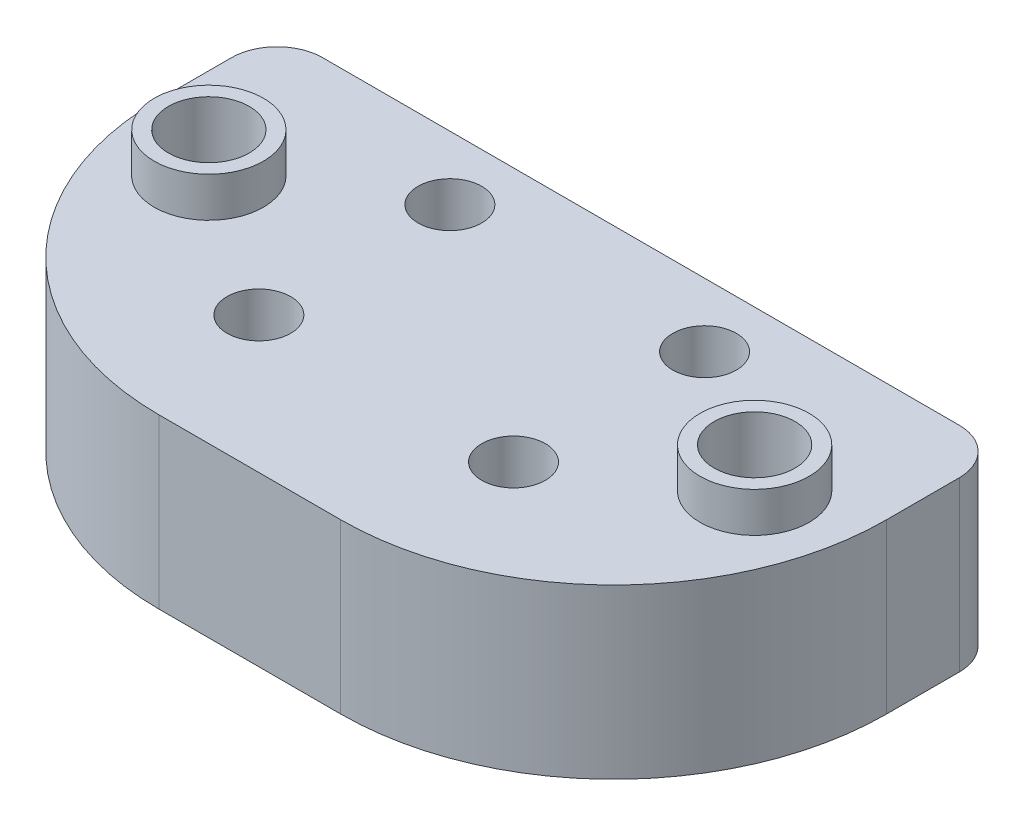
SolidWorks part; units mm, degrees
ref_plane "Front Plane" through (0, 0, 0) normal (0, 0, 1) x (1, 0, 0)
ref_plane "Top Plane" through (0, 0, 0) normal (0, 1, 0) x (1, 0, 0)
ref_plane "Right Plane" through (0, 0, 0) normal (1, 0, 0) x (0, 0, -1)
sketch "Sketch1" plane through (0, 0, 0) normal (0, 1, 0) x (1, 0, 0)
  line L0 (60, -8) -> (80, -8)
  line L1 (0, 0) -> (80, 0)
  line L2 (0, 0) -> (0, -51)
  line L3 (0, -51) -> (80, -51)
  line L4 (80, 0) -> (80, -51)
  line L5 (20, -8) -> (60, -8)
  line L6 (20, -8) -> (20, -43)
  line L7 (20, -43) -> (60, -43)
  line L8 (60, -8) -> (60, -43)
  line L9 (0, -8) -> (20, -8)
  circle A0 centre (26, -15) radius 3.5
  circle A1 centre (54, -15) radius 3.5
  circle A2 centre (54, -36) radius 3.5
  circle A3 centre (26, -36) radius 3.5
  circle A4 centre (10, -25.5) radius 4.445
  circle A5 centre (70, -25.5) radius 4.445
  circle A6 centre (26, -15) radius 4.35
  circle A7 centre (54, -15) radius 4.35
  circle A8 centre (26, -36) radius 4.35
  circle A9 centre (54, -36) radius 4.35
  circle A10 centre (70, -25.5) radius 6
  circle A11 centre (10, -25.5) radius 6
  dimension "D7" = 7
  dimension "D8" = 8.89
  dimension "D16" = 8.7
  dimension "D17" = 12
  dimension "D1" = 21
  dimension "D2" = 28
  dimension "D3" = 26
  dimension "D4" = 80
  dimension "D5" = 51
  dimension "D6" = 15
  dimension "D9" = 10
  dimension "D10" = 10
  dimension "D11" = 40
  dimension "D12" = 35
  dimension "D13" = 7
  dimension "D14" = 6
  dimension "D15" = 25.5
extrude "Boss-Extrude1" add sketch "Sketch1" along normal blind 18.5 contours L4 L1 L2 L3 A5 A4 L5 L8 L7 L6 | L8 L5 L6 L7 A9 A8 A7 A6 | A6 A0 | A7 A1 | A9 A2 | A8 A3 | A10 A5 | A11 A4 region at (40, 0, 25.5) region at (70, 0, 8.9082) region at (21.773, 0, 15) region at (49.773, 0, 15) region at (21.773, 0, 36) region at (49.773, 0, 36) region at (64.1697, 0, 25.5) region at (4.1697, 0, 25.5)
extrude "Cut-Extrude1" cut sketch "Sketch1<4>" along normal blind 6 contours A6 A0 | A7 A1 | A9 A2 | A8 A3 region at (21.773, 0, 15) region at (49.773, 0, 15) region at (21.773, 0, 36) region at (49.773, 0, 36)
sketch "Sketch1<4>" plane through (0, 0, 0) normal (0, 1, 0) x (1, 0, 0) same geometry as "Sketch1"
fillet "Fillet1" radius 30 2 edges at (80, 9.25, 51) (0, 9.25, 51)
fillet "Fillet2" radius 5 2 edges at (0, 9.25, 8) (80, 9.25, 8)
extrude "Boss-Extrude2" add sketch "Sketch1<5>" along normal blind 4.3864 from offset 18.5 contours A10 A5 | A11 A4 region at (64.1697, 0, 25.5) region at (4.1697, 0, 25.5)
sketch "Sketch1<5>" plane through (0, 0, 0) normal (0, 1, 0) x (1, 0, 0) same geometry as "Sketch1"
equation "\"D3@Sketch1\"=(\"D4@Sketch1\"-\"D2@Sketch1\")/2"
equation "\"D6@Sketch1\"=(\"D5@Sketch1\"-\"D1@Sketch1\")/2"
equation "\"D10@Sketch1\"=\"D9@Sketch1\""
equation "\"D14@Sketch1\"=(\"D11@Sketch1\"-\"D2@Sketch1\")/2"
equation "\"D13@Sketch1\"=(\"D12@Sketch1\"-\"D1@Sketch1\")/2"
equation "\"D15@Sketch1\"=\"D5@Sketch1\"/2"
